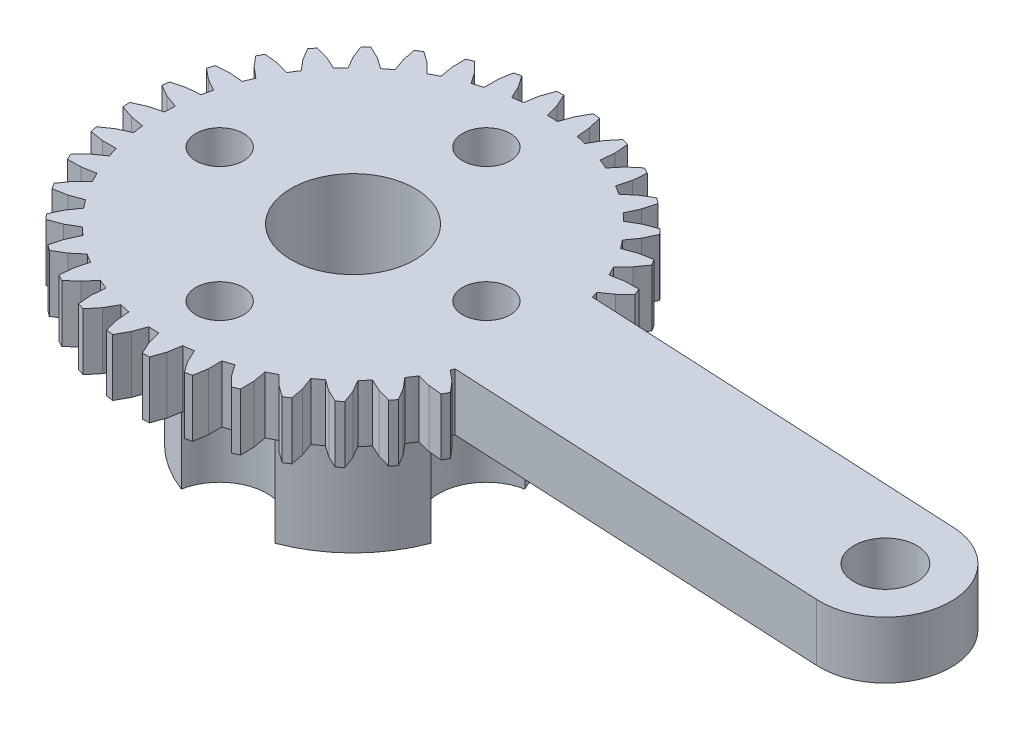
SolidWorks part; units mm, degrees
ref_plane "前视基准面" through (0, 0, 0) normal (0, 0, 1) x (1, 0, 0)
ref_plane "上视基准面" through (0, 0, 0) normal (0, 1, 0) x (1, 0, 0)
ref_plane "右视基准面" through (0, 0, 0) normal (1, 0, 0) x (0, 0, -1)
other "Configuration Table"
sketch "草图1" plane through (0, 0, 0) normal (0, 1, 0) x (1, 0, 0)
  line L0 (4.0827, 9.1823) -> (4.5422, 9.734)
  line L1 (0, 0) -> (9.6021, 2.9634) construction
  line L2 (4.5422, 9.734) -> (5.0868, 10.2019)
  line L3 (5.0868, 10.2019) -> (5.4091, 10.0347)
  line L4 (5.248, 10.1183) -> (4.4599, 8.5989) construction
  line L5 (5.3403, 9.32) -> (5.4091, 10.0347)
  line L6 (5.1541, 8.6266) -> (5.3403, 9.32)
  line L7 (5.6151, 8.3338) -> (6.1635, 8.7973)
  line L8 (6.1635, 8.7973) -> (6.781, 9.1636)
  line L9 (6.781, 9.1636) -> (7.0695, 8.9429)
  line L10 (6.8776, 8.2511) -> (7.0695, 8.9429)
  line L11 (6.5738, 7.6005) -> (6.8776, 8.2511)
  line L12 (6.977, 7.2322) -> (7.5975, 7.5934)
  line L13 (7.5975, 7.5934) -> (8.2693, 7.8469)
  line L14 (8.2693, 7.8469) -> (8.515, 7.5795)
  line L15 (8.2059, 6.9314) -> (8.515, 7.5795)
  line L16 (7.7937, 6.3435) -> (8.2059, 6.9314)
  line L17 (8.1268, 5.9108) -> (8.8006, 6.1588)
  line L18 (8.8006, 6.1588) -> (9.5062, 6.2917)
  line L19 (9.5062, 6.2917) -> (9.7018, 5.9857)
  line L20 (9.2849, 5.4012) -> (9.7018, 5.9857)
  line L21 (8.7769, 4.8938) -> (9.2849, 5.4012)
  line L22 (9.0298, 4.4098) -> (9.7364, 4.537)
  line L23 (9.7364, 4.537) -> (10.4543, 4.5454)
  line L24 (10.4543, 4.5454) -> (10.5938, 4.2101)
  line L25 (10.0817, 3.7068) -> (10.5938, 4.2101)
  line L26 (9.4933, 3.2953) -> (10.0817, 3.7068)
  line L47 (9.1823, -4.0827) -> (9.734, -4.5422)
  line L48 (9.734, -4.5422) -> (10.2019, -5.0868)
  line L49 (10.2019, -5.0868) -> (10.0347, -5.4091)
  line L50 (9.32, -5.3403) -> (10.0347, -5.4091)
  line L51 (8.6266, -5.1541) -> (9.32, -5.3403)
  line L52 (8.3338, -5.6151) -> (8.7973, -6.1635)
  line L53 (8.7973, -6.1635) -> (9.1636, -6.781)
  line L54 (9.1636, -6.781) -> (8.9429, -7.0695)
  line L55 (8.2511, -6.8776) -> (8.9429, -7.0695)
  line L56 (7.6005, -6.5738) -> (8.2511, -6.8776)
  line L57 (7.2322, -6.977) -> (7.5934, -7.5975)
  line L58 (7.5934, -7.5975) -> (7.8469, -8.2693)
  line L59 (7.8469, -8.2693) -> (7.5795, -8.515)
  line L60 (6.9314, -8.2059) -> (7.5795, -8.515)
  line L61 (6.3435, -7.7937) -> (6.9314, -8.2059)
  line L62 (5.9108, -8.1268) -> (6.1588, -8.8006)
  line L63 (6.1588, -8.8006) -> (6.2917, -9.5062)
  line L64 (6.2917, -9.5062) -> (5.9857, -9.7018)
  line L65 (5.4012, -9.2849) -> (5.9857, -9.7018)
  line L66 (4.8938, -8.7769) -> (5.4012, -9.2849)
  line L67 (4.4098, -9.0298) -> (4.537, -9.7364)
  line L68 (4.537, -9.7364) -> (4.5454, -10.4543)
  line L69 (4.5454, -10.4543) -> (4.2101, -10.5938)
  line L70 (3.7068, -10.0817) -> (4.2101, -10.5938)
  line L71 (3.2953, -9.4933) -> (3.7068, -10.0817)
  line L72 (2.7748, -9.6583) -> (2.7773, -10.3763)
  line L73 (2.7773, -10.3763) -> (2.6609, -11.0848)
  line L74 (2.6609, -11.0848) -> (2.3065, -11.1639)
  line L75 (1.8998, -10.5722) -> (2.3065, -11.1639)
  line L76 (1.5968, -9.9213) -> (1.8998, -10.5722)
  line L77 (1.0555, -9.9934) -> (0.9333, -10.701)
  line L78 (0.9333, -10.701) -> (0.6957, -11.3785)
  line L79 (0.6957, -11.3785) -> (0.3329, -11.3949)
  line L80 (0.0351, -10.7415) -> (0.3329, -11.3949)
  line L81 (-0.1503, -10.0479) -> (0.0351, -10.7415)
  line L82 (-0.6959, -10.0249) -> (-0.9391, -10.7005)
  line L83 (-0.9391, -10.7005) -> (-1.2908, -11.3264)
  line L84 (-1.2908, -11.3264) -> (-1.6509, -11.2796)
  line L85 (-1.8307, -10.5844) -> (-1.6509, -11.2796)
  line L86 (-1.8928, -9.8691) -> (-1.8307, -10.5844)
  line L87 (-2.4261, -9.7517) -> (-2.7829, -10.3748)
  line L88 (-2.7829, -10.3748) -> (-3.238, -10.9302)
  line L89 (-3.238, -10.9302) -> (-3.5845, -10.8215)
  line L90 (-3.6408, -10.1057) -> (-3.5845, -10.8215)
  line L91 (-3.5778, -9.3905) -> (-3.6408, -10.1057)
  line L92 (-4.0827, -9.1823) -> (-4.5422, -9.734)
  line L93 (-4.5422, -9.734) -> (-5.0868, -10.2019)
  line L94 (-5.0868, -10.2019) -> (-5.4091, -10.0347)
  line L95 (-5.3403, -9.32) -> (-5.4091, -10.0347)
  line L96 (-5.1541, -8.6266) -> (-5.3403, -9.32)
  line L97 (-5.6151, -8.3338) -> (-6.1635, -8.7973)
  line L98 (-6.1635, -8.7973) -> (-6.781, -9.1636)
  line L99 (-6.781, -9.1636) -> (-7.0695, -8.9429)
  line L100 (-6.8776, -8.2511) -> (-7.0695, -8.9429)
  line L101 (-6.5738, -7.6005) -> (-6.8776, -8.2511)
  line L102 (-6.977, -7.2322) -> (-7.5975, -7.5934)
  line L103 (-7.5975, -7.5934) -> (-8.2693, -7.8469)
  line L104 (-8.2693, -7.8469) -> (-8.515, -7.5795)
  line L105 (-8.2059, -6.9314) -> (-8.515, -7.5795)
  line L106 (-7.7937, -6.3435) -> (-8.2059, -6.9314)
  line L107 (-8.1268, -5.9108) -> (-8.8006, -6.1588)
  line L108 (-8.8006, -6.1588) -> (-9.5062, -6.2917)
  line L109 (-9.5062, -6.2917) -> (-9.7018, -5.9857)
  line L110 (-9.2849, -5.4012) -> (-9.7018, -5.9857)
  line L111 (-8.7769, -4.8938) -> (-9.2849, -5.4012)
  line L112 (-9.0298, -4.4098) -> (-9.7364, -4.537)
  line L113 (-9.7364, -4.537) -> (-10.4543, -4.5454)
  line L114 (-10.4543, -4.5454) -> (-10.5938, -4.2101)
  line L115 (-10.0817, -3.7068) -> (-10.5938, -4.2101)
  line L116 (-9.4933, -3.2953) -> (-10.0817, -3.7068)
  line L117 (-9.6583, -2.7748) -> (-10.3763, -2.7773)
  line L118 (-10.3763, -2.7773) -> (-11.0848, -2.6609)
  line L119 (-11.0848, -2.6609) -> (-11.1639, -2.3065)
  line L120 (-10.5722, -1.8998) -> (-11.1639, -2.3065)
  line L121 (-9.9213, -1.5968) -> (-10.5722, -1.8998)
  line L122 (-9.9934, -1.0555) -> (-10.701, -0.9333)
  line L123 (-10.701, -0.9333) -> (-11.3785, -0.6957)
  line L124 (-11.3785, -0.6957) -> (-11.3949, -0.3329)
  line L125 (-10.7415, -0.0351) -> (-11.3949, -0.3329)
  line L126 (-10.0479, 0.1503) -> (-10.7415, -0.0351)
  line L127 (-10.0249, 0.6959) -> (-10.7005, 0.9391)
  line L128 (-10.7005, 0.9391) -> (-11.3264, 1.2908)
  line L129 (-11.3264, 1.2908) -> (-11.2796, 1.6509)
  line L130 (-10.5844, 1.8307) -> (-11.2796, 1.6509)
  line L131 (-9.8691, 1.8928) -> (-10.5844, 1.8307)
  line L132 (-9.7517, 2.4261) -> (-10.3748, 2.7829)
  line L133 (-10.3748, 2.7829) -> (-10.9302, 3.238)
  line L134 (-10.9302, 3.238) -> (-10.8215, 3.5845)
  line L135 (-10.1057, 3.6408) -> (-10.8215, 3.5845)
  line L136 (-9.3905, 3.5778) -> (-10.1057, 3.6408)
  line L137 (-9.1823, 4.0827) -> (-9.734, 4.5422)
  line L138 (-9.734, 4.5422) -> (-10.2019, 5.0868)
  line L139 (-10.2019, 5.0868) -> (-10.0347, 5.4091)
  line L140 (-9.32, 5.3403) -> (-10.0347, 5.4091)
  line L141 (-8.6266, 5.1541) -> (-9.32, 5.3403)
  line L142 (-8.3338, 5.6151) -> (-8.7973, 6.1635)
  line L143 (-8.7973, 6.1635) -> (-9.1636, 6.781)
  line L144 (-9.1636, 6.781) -> (-8.9429, 7.0695)
  line L145 (-8.2511, 6.8776) -> (-8.9429, 7.0695)
  line L146 (-7.6005, 6.5738) -> (-8.2511, 6.8776)
  line L147 (-7.2322, 6.977) -> (-7.5934, 7.5975)
  line L148 (-7.5934, 7.5975) -> (-7.8469, 8.2693)
  line L149 (-7.8469, 8.2693) -> (-7.5795, 8.515)
  line L150 (-6.9314, 8.2059) -> (-7.5795, 8.515)
  line L151 (-6.3435, 7.7937) -> (-6.9314, 8.2059)
  line L152 (-5.9108, 8.1268) -> (-6.1588, 8.8006)
  line L153 (-6.1588, 8.8006) -> (-6.2917, 9.5062)
  line L154 (-6.2917, 9.5062) -> (-5.9857, 9.7018)
  line L155 (-5.4012, 9.2849) -> (-5.9857, 9.7018)
  line L156 (-4.8938, 8.7769) -> (-5.4012, 9.2849)
  line L157 (-4.4098, 9.0298) -> (-4.537, 9.7364)
  line L158 (-4.537, 9.7364) -> (-4.5454, 10.4543)
  line L159 (-4.5454, 10.4543) -> (-4.2101, 10.5938)
  line L160 (-3.7068, 10.0817) -> (-4.2101, 10.5938)
  line L161 (-3.2953, 9.4933) -> (-3.7068, 10.0817)
  line L162 (-2.7748, 9.6583) -> (-2.7773, 10.3763)
  line L163 (-2.7773, 10.3763) -> (-2.6609, 11.0848)
  line L164 (-2.6609, 11.0848) -> (-2.3065, 11.1639)
  line L165 (-1.8998, 10.5722) -> (-2.3065, 11.1639)
  line L166 (-1.5968, 9.9213) -> (-1.8998, 10.5722)
  line L167 (-1.0555, 9.9934) -> (-0.9333, 10.701)
  line L168 (-0.9333, 10.701) -> (-0.6957, 11.3785)
  line L169 (-0.6957, 11.3785) -> (-0.3329, 11.3949)
  line L170 (-0.0351, 10.7415) -> (-0.3329, 11.3949)
  line L171 (0.1503, 10.0479) -> (-0.0351, 10.7415)
  line L172 (0.6959, 10.0249) -> (0.9391, 10.7005)
  line L173 (0.9391, 10.7005) -> (1.2908, 11.3264)
  line L174 (1.2908, 11.3264) -> (1.6509, 11.2796)
  line L175 (1.8307, 10.5844) -> (1.6509, 11.2796)
  line L176 (1.8928, 9.8691) -> (1.8307, 10.5844)
  line L177 (2.4261, 9.7517) -> (2.7829, 10.3748)
  line L178 (2.7829, 10.3748) -> (3.238, 10.9302)
  line L179 (3.238, 10.9302) -> (3.5845, 10.8215)
  line L180 (3.6408, 10.1057) -> (3.5845, 10.8215)
  line L181 (3.5778, 9.3905) -> (3.6408, 10.1057)
  line L182 (5.1731, 8.6974) -> (5.2626, 8.6577) construction
  line L183 (0, 0) -> (29.4066, -1.4634) construction
  line L185 (9.6021, 2.9634) -> (29.5774, 1.9693)
  line L186 (9.2605, -3.9021) -> (29.2357, -4.8962)
  line L188 (0, 0) -> (9.2605, -3.9021) construction
  line L189 (9.6583, 2.7748) -> (10.3763, 2.7773) [skipped]
  line L190 (10.3763, 2.7773) -> (11.0848, 2.6609) [skipped]
  line L191 (11.0848, 2.6609) -> (11.1639, 2.3065) [skipped]
  line L192 (10.5722, 1.8998) -> (11.1639, 2.3065) [skipped]
  line L193 (9.9213, 1.5968) -> (10.5722, 1.8998) [skipped]
  line L194 (9.9934, 1.0555) -> (10.701, 0.9333) [skipped]
  line L195 (10.701, 0.9333) -> (11.3785, 0.6957) [skipped]
  line L196 (11.3785, 0.6957) -> (11.3949, 0.3329) [skipped]
  line L197 (10.7415, 0.0351) -> (11.3949, 0.3329) [skipped]
  line L198 (10.0479, -0.1503) -> (10.7415, 0.0351) [skipped]
  line L199 (9.7517, -2.4261) -> (10.3748, -2.7829) [skipped]
  line L200 (10.3748, -2.7829) -> (10.9302, -3.238) [skipped]
  line L201 (10.9302, -3.238) -> (10.8215, -3.5845) [skipped]
  line L202 (10.1057, -3.6408) -> (10.8215, -3.5845) [skipped]
  line L203 (9.3905, -3.5778) -> (10.1057, -3.6408) [skipped]
  line L204 (10.5844, -1.8307) -> (11.2796, -1.6509) [skipped]
  line L205 (11.3264, -1.2908) -> (11.2796, -1.6509) [skipped]
  line L206 (10.7005, -0.9391) -> (11.3264, -1.2908) [skipped]
  line L207 (10.0249, -0.6959) -> (10.7005, -0.9391) [skipped]
  line L208 (9.8691, -1.8928) -> (10.5844, -1.8307) [skipped]
  arc A0 (-5.9108, 8.1268) -> (-6.3435, 7.7937) centre (0, 0) ccw
  arc A1 (-4.4098, 9.0298) -> (-4.8938, 8.7769) centre (0, 0) ccw
  arc A2 (-2.7748, 9.6583) -> (-3.2953, 9.4933) centre (0, 0) ccw
  arc A3 (-1.0555, 9.9934) -> (-1.5968, 9.9213) centre (0, 0) ccw
  arc A4 (-7.2322, 6.977) -> (-7.6005, 6.5738) centre (0, 0) ccw
  arc A5 (-8.3338, 5.6151) -> (-8.6266, 5.1541) centre (0, 0) ccw
  arc A6 (-9.1823, 4.0827) -> (-9.3905, 3.5778) centre (0, 0) ccw
  arc A7 (-9.7517, 2.4261) -> (-9.8691, 1.8928) centre (0, 0) ccw
  arc A8 (-10.0249, 0.6959) -> (-10.0479, 0.1503) centre (0, 0) ccw
  arc A9 (-9.9934, -1.0555) -> (-9.9213, -1.5968) centre (0, 0) ccw
  arc A10 (-9.6583, -2.7748) -> (-9.4933, -3.2953) centre (0, 0) ccw
  arc A11 (-9.0298, -4.4098) -> (-8.7769, -4.8938) centre (0, 0) ccw
  arc A12 (-8.1268, -5.9108) -> (-7.7937, -6.3435) centre (0, 0) ccw
  arc A13 (-6.977, -7.2322) -> (-6.5738, -7.6005) centre (0, 0) ccw
  arc A14 (-5.6151, -8.3338) -> (-5.1541, -8.6266) centre (0, 0) ccw
  arc A15 (-4.0827, -9.1823) -> (-3.5778, -9.3905) centre (0, 0) ccw
  arc A16 (-2.4261, -9.7517) -> (-1.8928, -9.8691) centre (0, 0) ccw
  arc A17 (-0.6959, -10.0249) -> (-0.1503, -10.0479) centre (0, 0) ccw
  arc A18 (1.0555, -9.9934) -> (1.5968, -9.9213) centre (0, 0) ccw
  arc A19 (2.7748, -9.6583) -> (3.2953, -9.4933) centre (0, 0) ccw
  arc A20 (4.4098, -9.0298) -> (4.8938, -8.7769) centre (0, 0) ccw
  arc A21 (5.9108, -8.1268) -> (6.3435, -7.7937) centre (0, 0) ccw
  arc A22 (7.2322, -6.977) -> (7.6005, -6.5738) centre (0, 0) ccw
  arc A23 (8.3338, -5.6151) -> (8.6266, -5.1541) centre (0, 0) ccw
  arc A24 (9.1823, -4.0827) -> (9.2605, -3.9021) centre (0, 0) ccw
  arc A28 (0.6959, 10.0249) -> (0.1503, 10.0479) centre (0, 0) ccw
  arc A29 (2.4261, 9.7517) -> (1.8928, 9.8691) centre (0, 0) ccw
  arc A30 (4.0827, 9.1823) -> (3.5778, 9.3905) centre (0, 0) ccw
  arc A31 (5.6151, 8.3338) -> (5.1541, 8.6266) centre (0, 0) ccw
  arc A32 (6.977, 7.2322) -> (6.5738, 7.6005) centre (0, 0) ccw
  arc A33 (8.1268, 5.9108) -> (7.7937, 6.3435) centre (0, 0) ccw
  arc A34 (9.0298, 4.4098) -> (8.7769, 4.8938) centre (0, 0) ccw
  arc A35 (9.6021, 2.9634) -> (9.4933, 3.2953) centre (0, 0) ccw
  arc A36 (29.2357, -4.8962) -> (29.5774, 1.9693) centre (29.4066, -1.4634) ccw
  circle A37 centre (29.4066, -1.4634) radius 1.65
  circle A38 centre (0, 0) radius 1.65
  circle A39 centre (0, 0) radius 7 construction
  circle A44 centre (0, 0) radius 10.7416 construction
  point P51 (0, 0)
  point P224 (0, 0)
  dimension "D1" = 20.098
  dimension "D10" = 3.3
  dimension "D11" = 3.3
  dimension "D14" = 14
  dimension "D2" = 0.718
  dimension "D3" = 20
  dimension "D4" = 170.464
  dimension "D5" = 0.718
  dimension "D6" = 111.916
  dimension "D7" = 36
  dimension "D8" = 20
  dimension "D9" = 6.8739
extrude "凸台-拉伸1" add sketch "草图1" along normal blind 3
sketch "草图2" plane through (0, 3, 0) normal (0, 1, 0) x (1, 0, 0)
  circle A0 centre (0, 0) radius 10.7416 construction
sketch "草图4" plane through (0, 0, 0) normal (0, -1, 0) x (1, 0, 0)
  circle A0 centre (0, 0) radius 1.65
  circle A1 centre (0, 0) radius 7
  circle A2 centre (0, 0) radius 1.65 construction
  dimension "D1" = 14
extrude "凸台-拉伸3" add sketch "草图4" along normal blind 7
sketch "草图5" plane through (0, 0, 0) normal (0, -1, 0) x (1, 0, 0)
  circle A0 centre (0, 0) radius 7 construction
  circle A1 centre (7, 0) radius 1.25
  circle A2 centre (0, -7) radius 1.25
  circle A3 centre (-7, 0) radius 1.25
  circle A4 centre (0, 7) radius 1.25
  point P14 (0, 0)
  dimension "D1" = 14
  dimension "D2" = 2.5
  dimension "D3" = 4
extrude "切除-拉伸1" cut sketch "草图5" against normal through all and the other way blind 10
sketch "草图8" plane through (0, 0, 0) normal (0, -1, 0) x (1, 0, 0)
  circle A0 centre (0, 7) radius 2.5
  circle A1 centre (7, 0) radius 2.5
  circle A2 centre (0, -7) radius 2.5
  circle A3 centre (-7, 0) radius 2.5
  point P12 (0, 0)
  dimension "D1" = 5
  dimension "D2" = 4
extrude "切除-拉伸4" cut sketch "草图8" against normal blind 0.5 and the other way blind 10
sketch "草图9" plane through (0, 3, 0) normal (0, 1, 0) x (1, 0, 0)
  circle A0 centre (0, 0) radius 3.25
  dimension "D1" = 6.5
extrude "切除-拉伸5" cut sketch "草图9" against normal blind 5.5
